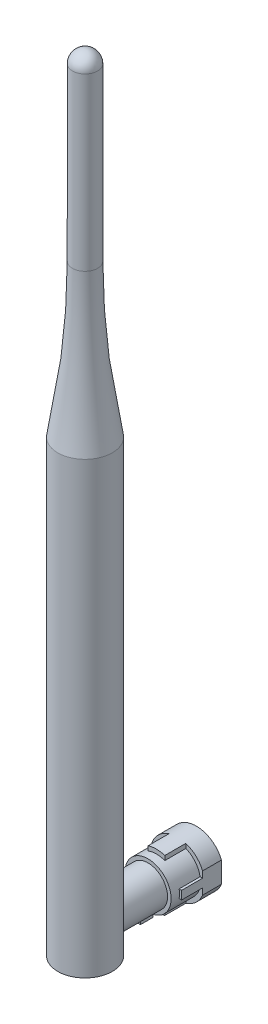
SolidWorks part; units mm, degrees
ref_plane "Front Plane" through (0, 0, 0) normal (0, 0, 1) x (1, 0, 0)
ref_plane "Top Plane" through (0, 0, 0) normal (0, 1, 0) x (1, 0, 0)
ref_plane "Right Plane" through (0, 0, 0) normal (1, 0, 0) x (0, 0, -1)
sketch "Sketch1" plane through (0, 0, 0) normal (0, 0, 1) x (1, 0, 0)
  line L0 (0, -8.0817) -> (0, 12.2151) construction
  line L1 (-6.6011, 0) -> (7.7733, 0) construction
  line L2 (-6, 2.5) -> (-6, -2.5)
  line L3 (6, 2.5) -> (6, -2.5)
  arc A0 (-6, -2.5) -> (6, -2.5) centre (0, 0) ccw
  arc A1 (6, 2.5) -> (-6, 2.5) centre (0, 0) ccw
  dimension "D1" = 13
  dimension "D2" = 6
extrude "Boss-Extrude1" add sketch "Sketch1" along normal blind 4.5
sketch "Sketch2" plane through (0, 0, 4.5) normal (0, 0, 1) x (1, 0, 0)
  line L0 (0, 6.5) -> (0, -6.5) construction
  line L1 (-6, 0) -> (6, 0) construction
  line L2 (-6, 2.5) -> (-6, -2.5) construction
  line L3 (6, -2.5) -> (6, 2.5) construction
  line L4 (-2, 6.1847) -> (-2, 5.1235)
  line L5 (-2, -5.1235) -> (-2, -6.1847)
  line L6 (2, -5.1235) -> (2, -6.1847)
  line L7 (2, 6.1847) -> (2, 5.1235)
  line L8 (-6, 1) -> (-5.4083, 1)
  line L9 (5.4083, 1) -> (6, 1)
  line L10 (5.4083, -1) -> (6, -1)
  line L11 (-6, -1) -> (-5.4083, -1)
  line L12 (6, -1) -> (6, 1)
  line L14 (6, -1) -> (6, 1)
  line L15 (6, 1) -> (6, -1)
  line L16 (-6, 1) -> (-6, -1)
  arc A0 (2, -5.1235) -> (5.4083, -1) centre (0, 0) ccw
  arc A1 (6, 2.5) -> (-6, 2.5) centre (0, 0) ccw construction
  arc A2 (-6, -2.5) -> (6, -2.5) centre (0, 0) ccw construction
  arc A3 (-2, 5.1235) -> (-5.4083, 1) centre (0, 0) ccw
  arc A4 (2, 6.1847) -> (-2, 6.1847) centre (0, 0) ccw
  arc A5 (-2, -6.1847) -> (2, -6.1847) centre (0, 0) ccw
  arc A6 (-5.4083, -1) -> (-2, -5.1235) centre (0, 0) ccw
  arc A7 (5.4083, 1) -> (2, 5.1235) centre (0, 0) ccw
  arc M14 (6, 2.5) -> (-6, 2.5) centre (0, 0) ccw
  line M15 (-6, 2.5) -> (-6, -2.5)
  arc M16 (-6, -2.5) -> (6, -2.5) centre (0, 0) ccw
  line M17 (6, -2.5) -> (6, 2.5)
  dimension "D1" = 11
  dimension "D2" = 4
  dimension "D3" = 2
extrude "Boss-Extrude2" add sketch "Sketch2" along normal blind 5 contours L9 A7 L7 L4 A3 L8 L11 A6 L5 L6 A0 L10 M14 M15 M16 M17 region at (0, 0, 4.5)
sketch "Sketch3" plane through (0, 0, 9.5) normal (0, 0, 1) x (1, 0, 0)
  circle A0 centre (0, 0) radius 5.5
extrude "Boss-Extrude3" add sketch "Sketch3" along normal blind 2
sketch "Sketch4" plane through (0, 0, 11.5) normal (0, 0, 1) x (1, 0, 0)
  line L0 (0, 0) -> (0, -6.5) construction
  line L1 (-1.2, -4.4925) -> (-1.2, -5.9925)
  line L2 (-1.2, -5.9925) -> (1.2, -5.9925)
  line L3 (1.2, -5.9925) -> (1.2, -4.4925)
  arc A0 (1.2, -4.4925) -> (-1.2, -4.4925) centre (0, 0) ccw
  arc A2 (-2, -6.1847) -> (2, -6.1847) centre (0, 0) ccw construction
  dimension "D1" = 9.3
  dimension "D2" = 1.2
  dimension "D3" = 1.2
  dimension "D4" = 1.5
extrude "Boss-Extrude4" add sketch "Sketch4" along normal blind 3
sketch "Sketch5" plane through (0, 0, 14.5) normal (0, 0, 1) x (1, 0, 0)
  circle A0 centre (0, 0) radius 4.65
extrude "Boss-Extrude5" add sketch "Sketch5" along normal blind 12
ref_point "Point1"
ref_plane "Plane1" through (0, 0, 0) normal (0, 1, 0) x (1, 0, 0)
sketch "Sketch6" plane through (0, 0, 0) normal (0, 1, 0) x (1, 0, 0)
  circle A0 centre (0, -26.5) radius 6.5
  dimension "D1" = 13
extrude "Boss-Extrude6" add sketch "Sketch6" along normal blind 100 and the other way blind 7
sketch "Sketch7" plane through (0, 100, 0) normal (0, 1, 0) x (1, 0, 0)
  circle A0 centre (0, -26.5) radius 3
  dimension "D1" = 6
extrude "Boss-Extrude7" add sketch "Sketch7" along normal blind 80
fillet "Fillet1" radius 190 1 edges at (0, 100, 29.5)
fillet "Fillet2" radius 3 1 edges at (0, 180, 29.5)
